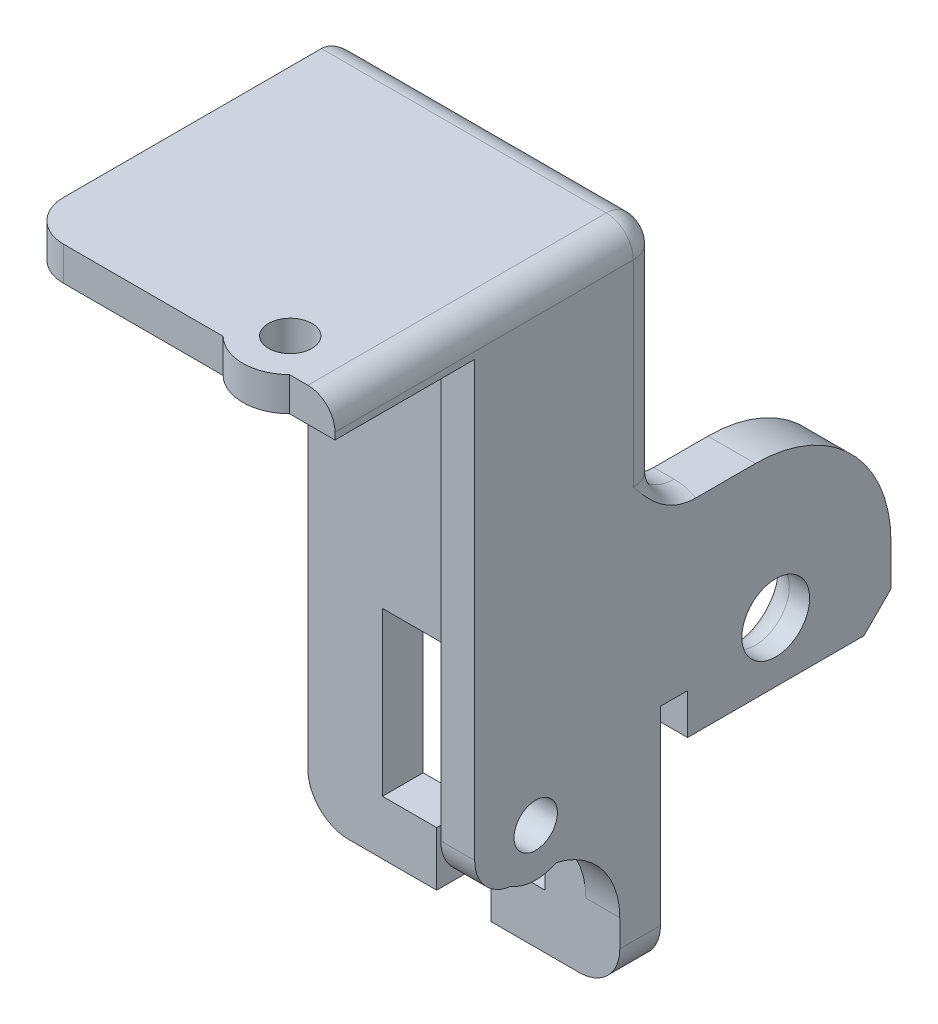
SolidWorks part; units mm, degrees
ref_plane "Alzado" through (0, 0, 0) normal (0, 0, 1) x (1, 0, 0)
ref_plane "Planta" through (0, 0, 0) normal (0, 1, 0) x (1, 0, 0)
ref_plane "Vista lateral" through (0, 0, 0) normal (1, 0, 0) x (0, 0, -1)
sketch "Croquis1" plane through (0, 0, 0) normal (0, 1, 0) x (1, 0, 0)
  line L0 (0, 2.5) -> (30.8, 2.5) construction
  line L1 (0, 0) -> (30.8, 0)
  line L2 (0, 0) -> (0, 5)
  line L3 (0, 5) -> (30.8, 5)
  line L4 (30.8, 0) -> (30.8, 5)
  circle A0 centre (3, 2.5) radius 1.6
  circle A1 centre (25, 2.5) radius 1.6
  dimension "D2" = 3.2
  dimension "D5" = 3.2
  dimension "D1" = 5
  dimension "D3" = 3
  dimension "D4" = 30.8
  dimension "D6" = 22
extrude "Saliente-Extruir1" add sketch "Croquis1" along normal blind 2.5
sketch "Croquis2" plane through (0, 0, 0) normal (0, -1, 0) x (1, 0, 0)
  line L1 (30.8, 0) -> (28.3, 0)
  line L2 (30.8, 0) -> (30.8, -24)
  line L3 (30.8, -24) -> (28.3, -24)
  line L4 (28.3, 0) -> (28.3, -24)
  dimension "D1" = 2.5
  dimension "D2" = 24
extrude "Saliente-Extruir2" add sketch "Croquis2" along normal blind 10
sketch "Croquis3" plane through (28.3, 0, 0) normal (-1, 0, 0) x (0, 0, 1)
  line L0 (-5, 0) -> (-24, 0) construction
  line L1 (-24, -10) -> (-21, -10)
  line L2 (-24, -10) -> (-24, 0)
  line L3 (-24, 0) -> (-21, 0)
  line L4 (-21, -10) -> (-21, 0)
  dimension "D1" = 3
extrude "Saliente-Extruir3" add sketch "Croquis3" along normal blind 20.5
sketch "Croquis4" plane through (0, -10, 0) normal (0, -1, 0) x (1, 0, 0)
  line L1 (30.8, -24) -> (7.8, -24)
  line L2 (30.8, -24) -> (30.8, -21)
  line L3 (30.8, -21) -> (7.8, -21)
  line L4 (7.8, -24) -> (7.8, -21)
extrude "Saliente-Extruir4" add sketch "Croquis4" along normal blind 45
sketch "Croquis6" plane through (0, 0, -24) normal (0, 0, -1) x (-1, 0, 0)
  line L1 (-30.8, -32) -> (-27.3, -32)
  line L2 (-30.8, -32) -> (-30.8, -17)
  line L3 (-30.8, -17) -> (-27.3, -17)
  line L4 (-27.3, -32) -> (-27.3, -17)
  line L5 (-7.8, -32) -> (-11.3, -32)
  line L6 (-7.8, -32) -> (-7.8, -17)
  line L7 (-7.8, -17) -> (-11.3, -17)
  line L8 (-11.3, -32) -> (-11.3, -17)
  line L9 (-7.8, -55) -> (-30.8, -55) construction
  line L10 (-30.8, -55) -> (-30.8, 0) construction
  line L11 (-7.8, 0) -> (-7.8, -55) construction
  point P16 (-29.05, -32)
  dimension "D1" = 3.5
  dimension "D2" = 15
  dimension "D3" = 15
  dimension "D4" = 3.5
  dimension "D5" = 23
extrude "Saliente-Extruir6" add sketch "Croquis6" along normal blind 17
sketch "Croquis7" plane through (11.3, 0, 0) normal (1, 0, 0) x (0, 0, -1)
  line L2 (41, -17) -> (41, -32) construction
  line L3 (41, -32) -> (24, -32) construction
  circle A0 centre (32.5, -27.6) radius 2.5
  dimension "D1" = 5
  dimension "D2" = 4.4
  dimension "D3" = 8.5
extrude "Cortar-Extruir1" cut sketch "Croquis7" against normal up to surface and the other way up to surface up to face at (7.8, -26, -27.5) other way up to face at (30.8, -18.5833, -19.1667)
fillet "Redondeo1" radius 2 2 edges at (27.3, -27.6, -35) (11.3, -30.1, -32.5)
sketch "Croquis8" plane through (0, 0, -5) normal (0, 0, -1) x (-1, 0, 0)
  line L1 (-30.8, 2.5) -> (-7.8, 2.5)
  line L2 (-30.8, 2.5) -> (-30.8, 0)
  line L3 (-30.8, 0) -> (-7.8, 0)
  line L4 (-7.8, 2.5) -> (-7.8, 0)
extrude "Saliente-Extruir7" add sketch "Croquis8" along normal up to surface (19 mm away) up to face at (19.3, -25.5, -24)
sketch "Croquis9" plane through (30.8, 0, 0) normal (1, 0, 0) x (0, 0, -1)
  line L0 (24, -17) -> (24, 2.5) construction
  line L1 (0, -10) -> (21, -10)
  line L2 (0, -10) -> (0, 0)
  line L3 (0, 0) -> (21, 0)
  line L4 (21, -10) -> (21, 0)
  line L5 (0, 2.5) -> (24, 2.5) construction
  dimension "D1" = 3
  dimension "D2" = 2.5
extrude "Cortar-Extruir2" cut sketch "Croquis9" against normal up to surface (2.5 mm away) up to face at (28.3, -5, -10.5)
sketch "Croquis10" plane through (0, 0, -21) normal (0, 0, 1) x (1, 0, 0)
  line L1 (30.8, 0) -> (28.3, 0)
  line L2 (30.8, 0) -> (30.8, -35)
  line L3 (30.8, -35) -> (28.3, -35)
  line L4 (28.3, 0) -> (28.3, -35)
  dimension "D1" = 2.5
  dimension "D2" = 35
extrude "Saliente-Extruir8" add sketch "Croquis10" along normal blind 10.7
sketch "Croquis11" plane through (0, 0, -24) normal (0, 0, -1) x (-1, 0, 0)
  line L0 (-11.3, -17) -> (-11.3, -32) construction
  line L1 (-13.3, -30) -> (-25.3, -30)
  line L2 (-13.3, -30) -> (-13.3, -42)
  line L3 (-13.3, -42) -> (-25.3, -42)
  line L4 (-25.3, -30) -> (-25.3, -42)
  line L5 (-27.3, -32) -> (-27.3, -17) construction
  line L6 (-7.8, -55) -> (-30.8, -55) construction
  dimension "D1" = 2
  dimension "D2" = 12
  dimension "D3" = 2
  dimension "D4" = 13
extrude "Cortar-Extruir3" cut sketch "Croquis11" against normal up to surface (3 mm away) up to face at (22.3, -30, -21)
sketch "Croquis12" plane through (30.8, 0, 0) normal (1, 0, 0) x (0, 0, -1)
  line L0 (10.3, -35) -> (21, -35) construction
  line L1 (10.3, -35) -> (10.3, 0) construction
  circle A0 centre (14.8, -32) radius 1.6
  dimension "D1" = 3.2
  dimension "D2" = 3
  dimension "D3" = 4.5
extrude "Cortar-Extruir4" cut sketch "Croquis12" against normal up to surface (2.5 mm away) up to face at (28.3, -17.5, -15.65)
fillet "Redondeo2" radius 6 1 edges at (29.55, -35, -21)
fillet "Redondeo6" radius 2 4 edges at (19.3, 2.5, -24) (30.8, 2.5, -12) (7.8, -7.25, -24) (30.8, -7.25, -24)
sketch "Croquis13" plane through (0, 0, -24) normal (0, 0, -1) x (-1, 0, 0)
  line L0 (-7.8, -32) -> (-7.8, -55) construction
  line L1 (-30.8, -55) -> (-7.8, -55)
  line L2 (-30.8, -55) -> (-30.8, -46)
  line L3 (-30.8, -46) -> (-21.3, -46)
  line L4 (-7.8, -55) -> (-7.8, -46)
  line L5 (-25.3, -42) -> (-13.3, -42) construction
  line L6 (-30.8, -55) -> (-30.8, -32) construction
  line L7 (-21.3, -42) -> (-17.3, -42)
  line L8 (-21.3, -42) -> (-21.3, -46)
  line L10 (-17.3, -42) -> (-17.3, -46)
  line L11 (-17.3, -46) -> (-7.8, -46)
  dimension "D1" = 4
  dimension "D2" = 4
  dimension "D3" = 9.5
extrude "Cortar-Extruir5" cut sketch "Croquis13" against normal up to surface (3 mm away) up to face at (19.3, -36, -21)
fillet "Redondeo7" radius 3 7 edges at (7.8, -46, -22.5) (30.8, -46, -22.5) (29.55, -35, -10.3) (8.3858, -17, -23.4142) (30.2142, -17, -23.4142) (10.55, -17, -24) (28.05, -17, -24)
sketch "Croquis15" plane through (0, -32, 0) normal (0, -1, 0) x (1, 0, 0)
  line L0 (30.8, -41) -> (30.8, -24) construction
  line L1 (30.8, -26) -> (7.8, -26)
  line L2 (30.8, -26) -> (30.8, -24)
  line L3 (30.8, -24) -> (7.8, -24)
  line L4 (7.8, -26) -> (7.8, -24)
  line L5 (7.8, -41) -> (7.8, -24) construction
  line L6 (11.3, -24) -> (7.8, -24) construction
  dimension "D1" = 2
extrude "Cortar-Extruir7" cut sketch "Croquis15" against normal blind 3
fillet "Redondeo9" radius 10 2 edges at (9.55, -17, -41) (29.05, -17, -41)
chamfer "Chaflán2" distance 2 angle 45 2 edges at (29.05, -32, -41) (9.55, -32, -41)
sketch "Croquis16" plane through (0, 2.5, 0) normal (0, 1, 0) x (1, 0, 0)
  circle A3 centre (25, 2.5) radius 3.5
  circle A4 centre (25, 2.5) radius 1.6 construction
  circle A5 centre (25, 2.5) radius 1.6
  dimension "D2" = 7
extrude "Saliente-Extruir9" add sketch "Croquis16" against normal up to surface (2.5 mm away) up to face at (3, 0, -0.9)
sketch "Croquis17" plane through (30.8, 0, 0) normal (1, 0, 0) x (0, 0, -1)
  circle A0 centre (14.8, -32) radius 3.5
  circle A1 centre (14.8, -32) radius 1.6 construction
  circle A2 centre (14.8, -32) radius 1.6
  dimension "D1" = 7
extrude "Saliente-Extruir10" add sketch "Croquis17" against normal up to surface (2.5 mm away) up to face at (28.3, -30.4, -14.8)
sketch "Croquis18" plane through (0, 2.5, 0) normal (0, 1, 0) x (1, 0, 0)
  line L1 (0, 0) -> (7.8, 0)
  line L2 (0, 0) -> (0, 5)
  line L3 (0, 5) -> (7.8, 5)
  line L4 (7.8, 0) -> (7.8, 5)
extrude "Cortar-Extruir8" cut sketch "Croquis18" against normal up to surface (2.5 mm away) up to face at (18.38, 0, -7.16)
fillet "Redondeo10" radius 3 1 edges at (7.8, 1.25, 0)
